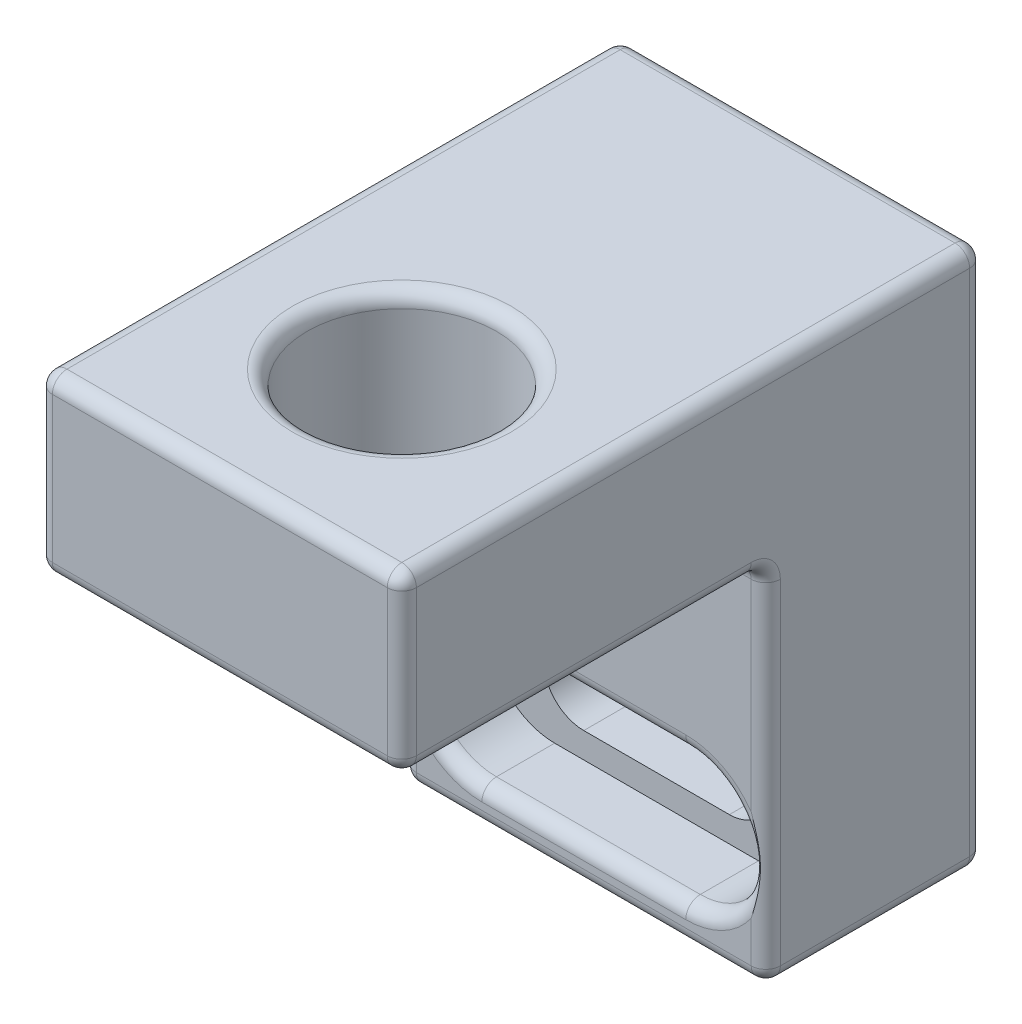
SolidWorks part; units mm, degrees
material "PLA"
ref_plane "Alzado" through (0, 0, 0) normal (0, 0, 1) x (1, 0, 0)
ref_plane "Planta" through (0, 0, 0) normal (0, 1, 0) x (1, 0, 0)
ref_plane "Vista lateral" through (0, 0, 0) normal (1, 0, 0) x (0, 0, -1)
sketch "Croquis1" plane through (0, 0, 0) normal (0, 0, 1) x (1, 0, 0)
  line L1 (12.5, 18.5) -> (-12.5, 18.5)
  line L2 (12.5, 18.5) -> (12.5, -18.5)
  line L3 (12.5, -18.5) -> (-12.5, -18.5)
  line L4 (-12.5, 18.5) -> (-12.5, -18.5)
  line L5 (12.5, 18.5) -> (-12.5, -18.5) construction
  line L6 (12.5, -18.5) -> (-12.5, 18.5) construction
  point P0 (0, 0)
  dimension "D1" = 37
  dimension "D2" = 25
extrude "Saliente-Extruir1" add sketch "Croquis1" along normal blind 20
sketch "Croquis2" plane through (0, 0, 20) normal (0, 0, 1) x (1, 0, 0)
  line L0 (12.5, -18.5) -> (12.5, 18.5) construction
  line L1 (-12.5, 18.5) -> (12.5, 18.5)
  line L2 (-12.5, 18.5) -> (-12.5, 6.5)
  line L3 (-12.5, 6.5) -> (12.5, 6.5)
  line L4 (12.5, 18.5) -> (12.5, 6.5)
  dimension "D1" = 12
extrude "Saliente-Extruir2" add sketch "Croquis2" along normal blind 20
sketch "Croquis3" plane through (0, 0, 20) normal (0, 0, 1) x (1, 0, 0)
  line L0 (-12.5, -11.5) -> (12.5, -11.5) construction
  line L1 (-12.5, 6.5) -> (-12.5, -18.5) construction
  line L2 (12.5, -18.5) -> (12.5, 6.5) construction
  line L3 (-12.5, -18.5) -> (12.5, -18.5) construction
  line L4 (-5, -11.5) -> (5, -11.5) construction
  line L5 (-5, -8.75) -> (5, -8.75)
  line L6 (-5, -14.25) -> (5, -14.25)
  arc A0 (-5, -8.75) -> (-5, -14.25) centre (-5, -11.5) ccw
  arc A1 (5, -14.25) -> (5, -8.75) centre (5, -11.5) ccw
  point P10 (0, -11.5)
  dimension "D1" = 7
  dimension "D2" = 5
  dimension "D3" = 12.5
  dimension "D4" = 5.5
extrude "Cortar-Extruir1" cut sketch "Croquis3" against normal blind 20
sketch "Croquis4" plane through (0, 0, 20) normal (0, 0, 1) x (1, 0, 0)
  line L0 (-12.5, -11.5) -> (12.5, -11.5) construction
  line L1 (-12.5, 6.5) -> (-12.5, -18.5) construction
  line L2 (12.5, -18.5) -> (12.5, 6.5) construction
  line L3 (-12.5, -18.5) -> (12.5, -18.5) construction
  line L4 (-7, -11.5) -> (7, -11.5) construction
  line L5 (-7, -7) -> (7, -7)
  line L6 (-7, -16) -> (7, -16)
  arc A0 (-7, -7) -> (-7, -16) centre (-7, -11.5) ccw
  arc A1 (7, -16) -> (7, -7) centre (7, -11.5) ccw
  point P10 (0, -11.5)
  dimension "D1" = 7
  dimension "D2" = 7
  dimension "D3" = 12.5
  dimension "D4" = 9
extrude "Cortar-Extruir2" cut sketch "Croquis4" against normal blind 10
sketch "Croquis5" plane through (0, 18.5, 0) normal (0, 1, 0) x (1, 0, 0)
  line L0 (0, 0) -> (0, -40) construction
  line L1 (12.5, 0) -> (-12.5, 0) construction
  line L2 (12.5, -40) -> (-12.5, -40) construction
  circle A0 centre (0, -27.5) radius 6.5
  dimension "D1" = 13
  dimension "D2" = 12.5
extrude "Cortar-Extruir3" cut sketch "Croquis5" against normal blind 18
sketch "Croquis6" plane through (12.5, 0, 0) normal (1, 0, 0) x (0, 0, -1)
  line L0 (-20, -18.5) -> (0, -18.5) construction
  line L1 (-20, 6.5) -> (-15, 6.5)
  line L2 (-20, 6.5) -> (-20, -18.5)
  line L3 (-20, -18.5) -> (-15, -18.5)
  line L4 (-15, 6.5) -> (-15, -18.5)
  dimension "D1" = 5
extrude "Cortar-Extruir4" cut sketch "Croquis6" against normal blind 28
fillet "Redondeo1" radius 1 24 edges at (0, -18.5, 0) (0, 6.5, 40) (0, 6.5, 34) (0, 6.5, 15) (0, -18.5, 15) (-11.5, -11.5, 15) (0, -16, 15) (11.5, -11.5, 15) (0, -7, 15) (0, 18.5, 40) (0, 18.5, 0) (-6.5, 18.5, 27.5) (-12.5, -18.5, 7.5) (-12.5, 0, 0) (-12.5, 18.5, 20) (-12.5, 12.5, 40) (-12.5, 6.5, 27.5) (-12.5, -6, 15) (12.5, 12.5, 40) (12.5, 18.5, 20) (12.5, 0, 0) (12.5, -18.5, 7.5) (12.5, -6, 15) (12.5, 6.5, 27.5)
